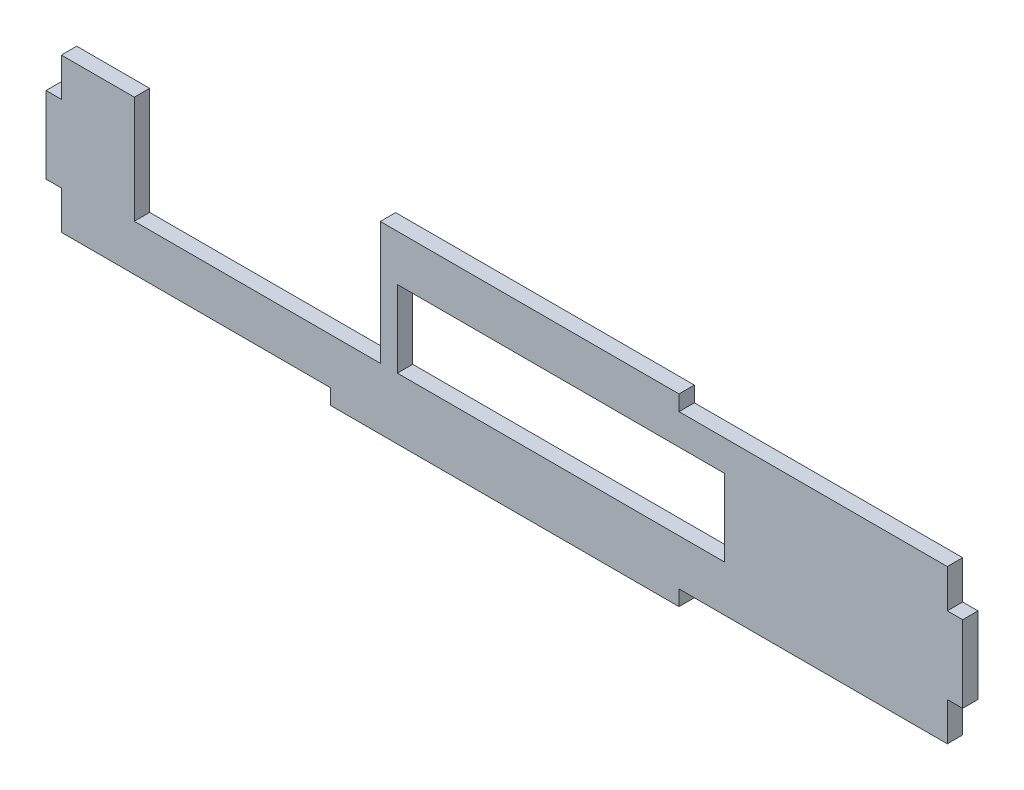
SolidWorks part; units mm, degrees
ref_plane "Front Plane" through (0, 0, 0) normal (0, 0, 1) x (1, 0, 0)
ref_plane "Top Plane" through (0, 0, 0) normal (0, 1, 0) x (1, 0, 0)
ref_plane "Right Plane" through (0, 0, 0) normal (1, 0, 0) x (0, 0, -1)
sketch "Sketch1" plane through (0, 0, 0) normal (0, 0, 1) x (1, 0, 0)
  line L0 (0, 20) -> (9.5, 20)
  line L5 (9.5, 5.9995) -> (41.5498, 5.9995)
  line L6 (9.5, 5.9995) -> (9.5, 20)
  line L8 (41.5498, 5.9995) -> (41.5498, 20)
  line L9 (86.41, 6) -> (43.7723, 6)
  line L10 (86.41, 6) -> (86.41, 16)
  line L11 (86.41, 16) -> (43.7723, 16)
  line L12 (43.7723, 6) -> (43.7723, 16)
  line L14 (0, 0) -> (35.0498, 0)
  line L15 (35.0498, 0) -> (35.0498, -2.0005)
  line L16 (35.0498, -2.0005) -> (80.4598, -2.0005)
  line L17 (80.4598, -2.0005) -> (80.4598, 0)
  line L18 (80.4598, 0) -> (115.41, 0)
  line L19 (0, 0) -> (0, 5)
  line L20 (0, 5) -> (-2, 5)
  line L21 (-2, 5) -> (-2, 15)
  line L22 (-2, 15) -> (0, 15)
  line L23 (0, 15) -> (0, 20)
  line L24 (115.41, 0) -> (115.41, 5)
  line L25 (115.41, 5) -> (117.41, 5)
  line L26 (117.41, 5) -> (117.41, 15)
  line L27 (117.41, 15) -> (115.41, 15)
  line L28 (115.41, 15) -> (115.41, 20)
  line L29 (80.4598, 20) -> (80.4598, 22)
  line L30 (80.4598, 22) -> (41.5498, 22)
  line L31 (41.5498, 22) -> (41.5498, 20)
  line L32 (80.4598, 20) -> (115.41, 20)
  dimension "D1" = 9.5
  dimension "D2" = 115.41
extrude "Boss-Extrude1" add sketch "Sketch1" along normal blind 2
